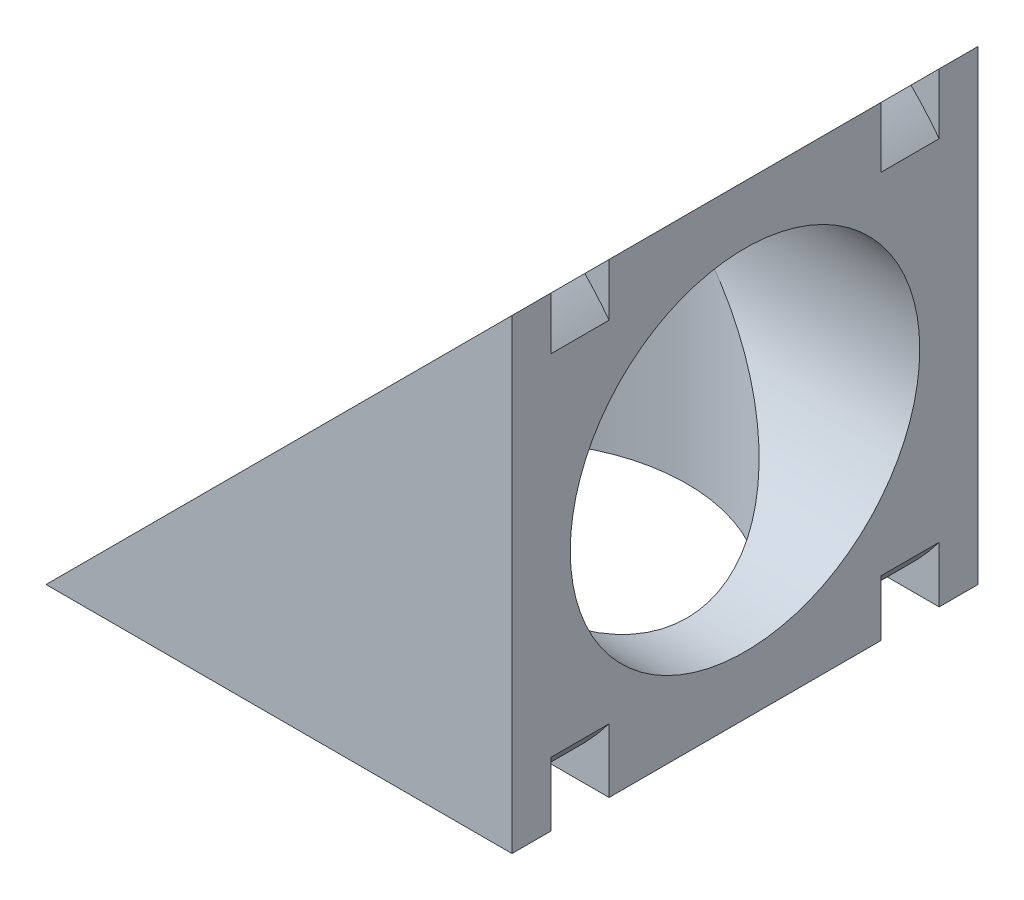
SolidWorks part; units mm, degrees
ref_plane "Спереди" through (0, 0, 0) normal (0, 0, 1) x (1, 0, 0)
ref_plane "Сверху" through (0, 0, 0) normal (0, 1, 0) x (1, 0, 0)
ref_plane "Справа" through (0, 0, 0) normal (1, 0, 0) x (0, 0, -1)
sketch "Эскиз1" plane through (0, 0, 0) normal (0, 1, 0) x (1, 0, 0)
  line L1 (-12, 12) -> (12, 12)
  line L2 (-12, 12) -> (-12, -12)
  line L3 (-12, -12) -> (12, -12)
  line L4 (12, 12) -> (12, -12)
  line L5 (-12, 12) -> (12, -12) construction
  line L6 (-12, -12) -> (12, 12) construction
  point P0 (0, 0)
  dimension "D1" = 24
  dimension "D2" = 24
extrude "Бобышка-Вытянуть1" add sketch "Эскиз1" along normal blind 24
ref_plane "Плоскость1" through (0, 12, 0) normal (0, 1, 0) x (1, 0, 0)
ref_axis "Ось1" through (0, 12, 50) along (0, 0, -1)
ref_plane "Плоскость2" through (-6, 6, 0) normal (-0.7071, 0.7071, 0) x (0.7071, 0.7071, 0)
sketch "Эскиз2" plane through (-6, 6, 0) normal (-0.7071, 0.7071, 0) x (0.7071, 0.7071, 0)
  line L1 (-35.866, 32.1628) -> (35.866, 32.1628)
  line L2 (-35.866, 32.1628) -> (-35.866, -32.1628)
  line L3 (-35.866, -32.1628) -> (35.866, -32.1628)
  line L4 (35.866, 32.1628) -> (35.866, -32.1628)
  line L5 (-35.866, 32.1628) -> (35.866, -32.1628) construction
  line L6 (-35.866, -32.1628) -> (35.866, 32.1628) construction
  point P0 (0, 0)
extrude "Вырез-Вытянуть1" cut sketch "Эскиз2" along normal blind 24
ref_axis "Ось2" through (12, 24, 12) along (-0.5774, -0.5774, -0.5774)
ref_axis "Ось3" through (12, 24, -12) along (-0.5774, -0.5774, 0.5774)
ref_point "Точка1"
sketch "Эскиз3" plane through (-6, 6, 0) normal (-0.7071, 0.7071, 0) x (0.7071, 0.7071, 0)
  line L1 (18.0353, 9.55) -> (-1.0647, 9.55)
  line L2 (18.0353, 9.55) -> (18.0353, -9.55)
  line L3 (18.0353, -9.55) -> (-1.0647, -9.55)
  line L4 (-1.0647, 9.55) -> (-1.0647, -9.55)
  line L5 (18.0353, 9.55) -> (-1.0647, -9.55) construction
  line L6 (18.0353, -9.55) -> (-1.0647, 9.55) construction
  point P0 (8.4853, 0)
  dimension "D1" = 19.1
  dimension "D2" = 19.1
extrude "Вырез-Вытянуть2" cut sketch "Эскиз3" against normal blind 0.75
ref_plane "Плоскость3" through (0, 0, 10) normal (0, 0, 1) x (1, 0, 0)
sketch "Эскиз4" plane through (0, 0, 10) normal (0, 0, 1) x (1, 0, 0)
  circle A0 centre (0, 12.2889) radius 15
  circle A1 centre (0, 12.2889) radius 20.3162
  dimension "D1" = 30
extrude "Вырез-Вытянуть3" cut sketch "Эскиз4" against normal blind 3
ref_plane "Плоскость4" through (0, 0, -10) normal (0, 0, 1) x (1, 0, 0)
sketch "Эскиз5" plane through (0, 0, -10) normal (0, 0, 1) x (1, 0, 0)
  circle A0 centre (0, 11.885) radius 15
  circle A1 centre (0, 11.885) radius 19.7788
  dimension "D1" = 30
extrude "Вырез-Вытянуть4" cut sketch "Эскиз5" along normal blind 3
sketch "Эскиз6" plane through (0, 0, 0) normal (0, 1, 0) x (1, 0, 0)
  circle A0 centre (0, 0) radius 1.2
  dimension "D1" = 2.4
extrude "Вырез-Вытянуть5" cut sketch "Эскиз6" along normal blind 8
sketch "Эскиз7" plane through (0, 0, 0) normal (1, 0, 0) x (0, 0, -1)
  line L1 (4.0368, -8) -> (-4.0368, -8)
  line L2 (4.0368, -8) -> (4.0368, 8)
  line L3 (4.0368, 8) -> (-4.0368, 8)
  line L4 (-4.0368, -8) -> (-4.0368, 8)
  line L5 (4.0368, -8) -> (-4.0368, 8) construction
  line L6 (4.0368, 8) -> (-4.0368, -8) construction
  point P0 (0, 0)
  dimension "D1" = 16
extrude "Вырез-Вытянуть6" cut sketch "Эскиз7" against normal blind 0.1 and the other way blind 0.1
sketch "Эскиз8" plane through (0, 0, 0) normal (0, 1, 0) x (1, 0, 0)
  circle A0 centre (0, 0) radius 9
  dimension "D1" = 18
extrude "Вырез-Вытянуть7" cut sketch "Эскиз8" along normal blind 30
sketch "Эскиз9" plane through (0, 0, 0) normal (1, 0, 0) x (0, 0, -1)
  circle A0 centre (0, 12) radius 9
  dimension "D1" = 18
extrude "Вырез-Вытянуть8" cut sketch "Эскиз9" along normal blind 30
